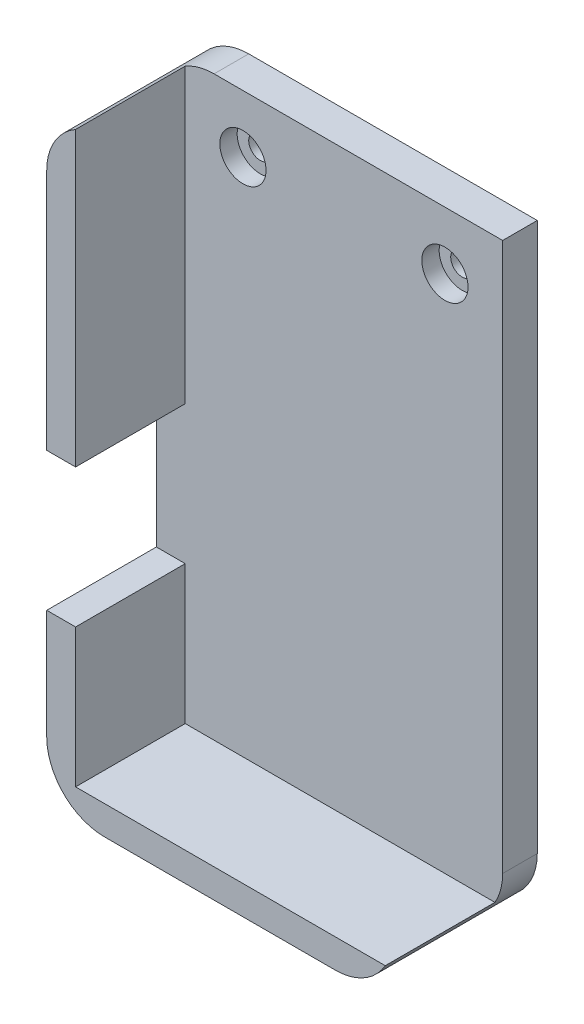
SolidWorks part; units mm, degrees
ref_plane "Front Plane" through (0, 0, 0) normal (0, 0, 1) x (1, 0, 0)
ref_plane "Top Plane" through (0, 0, 0) normal (0, 1, 0) x (1, 0, 0)
ref_plane "Right Plane" through (0, 0, 0) normal (1, 0, 0) x (0, 0, -1)
sketch "Sketch1" plane through (0, 0, 0) normal (0, 0, 1) x (1, 0, 0)
  line L0 (5, 105) -> (5, 5)
  line L1 (0, 0) -> (60, 0)
  line L2 (0, 0) -> (0, 105)
  line L5 (5, 5) -> (76, 5)
  line L7 (0, 105) -> (60, 105)
  line L8 (60, 105) -> (60, 0)
  circle A1 centre (50, 95) radius 2
  circle A2 centre (15, 95) radius 2
  circle A3 centre (15, 95) radius 4
  circle A4 centre (50, 95) radius 4
  dimension "D5" = 10
  dimension "D7" = 10
  dimension "D2" = 90
  dimension "D1" = 60
  dimension "D3" = 5
  dimension "D4" = 5
  dimension "100" = 105
  dimension "90" = 90
extrude "Boss-Extrude4" add sketch "Sketch1" along normal blind 6 contours L0 L5 A4 A3 | L5 L0 L2 L1 | A3 A2 | A2 | A4 A1 | A1 region at (32.5, 54.2553, 0) region at (3.7907, 55, 0) region at (50, 95, 0) region at (15, 95, 0) region at (11.1131, 95, 0) region at (46.1131, 95, 0)
extrude "Boss-Extrude5" add sketch "Sketch1<12>" along normal blind 25 contours L5 L0 L2 L1 region at (3.7907, 55, 0)
sketch "Sketch1<12>" plane through (0, 0, 0) normal (0, 0, 1) x (1, 0, 0) same geometry as "Sketch1"
extrude "Cut-Extrude1" cut sketch "Sketch1<15>" along normal blind 25 contours A2 | A1 region at (50, 95, 0) region at (15, 95, 0)
sketch "Sketch1<15>" plane through (0, 0, 0) normal (0, 0, 1) x (1, 0, 0) same geometry as "Sketch1"
extrude "Cut-Extrude2" cut sketch "Sketch1<16>" along normal blind 25 contours A4 A1 | A3 A2 region at (11.1131, 95, 0) region at (46.1131, 95, 0)
sketch "Sketch1<16>" plane through (0, 0, 0) normal (0, 0, 1) x (1, 0, 0) same geometry as "Sketch1"
extrude "Boss-Extrude7" add sketch "Sketch1<18>" along normal blind 3 contours A4 A1 | A3 A2 region at (11.1131, 95, 0) region at (46.1131, 95, 0)
sketch "Sketch1<18>" plane through (0, 0, 0) normal (0, 0, 1) x (1, 0, 0) same geometry as "Sketch1"
fillet "Fillet1" radius 10 3 edges at (60, 0, 12.5) (0, 105, 12.5) (0, 0, 12.5)
sketch "Sketch2" plane through (0, 0, 25) normal (0, 0, 1) x (1, 0, 0)
  line L0 (0, 10) -> (0, 95) construction
  line L1 (0, 29) -> (5, 29)
  line L2 (0, 29) -> (0, 53)
  line L3 (0, 53) -> (5, 53)
  line L4 (5, 29) -> (5, 53)
  line L5 (5, 103.6603) -> (5, 5) construction
  line L6 (58.6603, 5) -> (5, 5) construction
  dimension "D1" = 24
  dimension "D2" = 24
extrude "Cut-Extrude3" cut sketch "Sketch2" against normal blind 19
